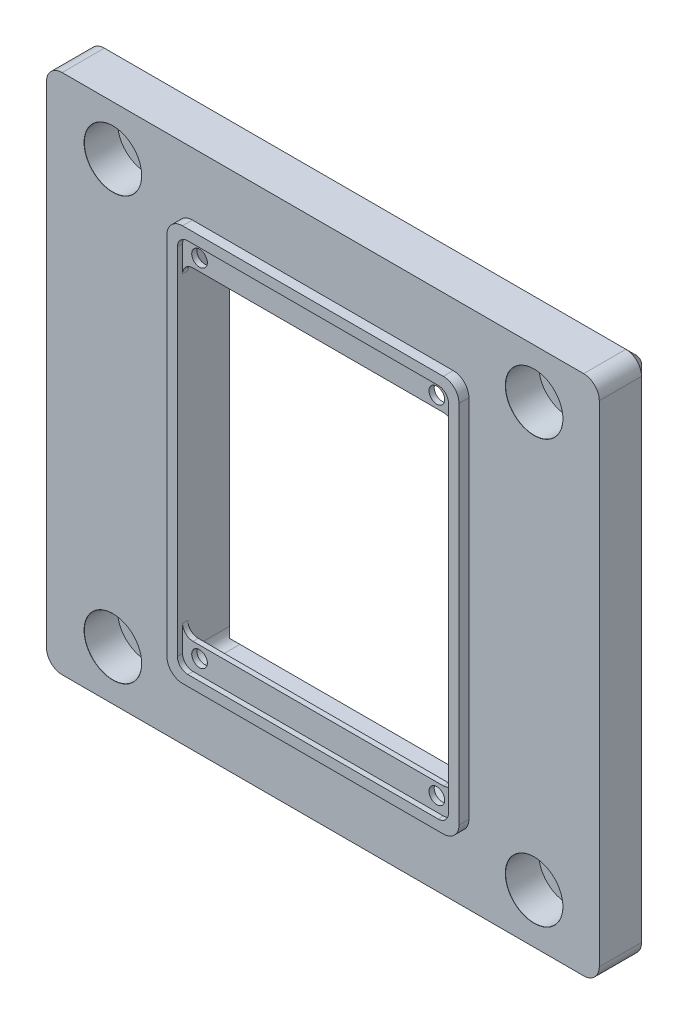
SolidWorks part; units mm, degrees
ref_plane "Front Plane" through (0, 0, 0) normal (1, 0, 0) x (0, 1, 0)
ref_plane "Top Plane" through (0, 0, 0) normal (0, 0, 1) x (0, 1, 0)
ref_plane "Right Plane" through (0, 0, 0) normal (0, 1, 0) x (-1, 0, 0)
sketch "Sketch1" plane through (0, 0, 0) normal (0, 0, 1) x (0, 1, 0)
  line L0 (33.4102, -36.8483) -> (45.4102, -61.8483)
  line L1 (-39.5237, 16.1988) -> (30.4763, 16.1988)
  line L2 (-39.5237, 16.1988) -> (-39.5237, -33.8012)
  line L3 (-39.5237, -33.8012) -> (30.4763, -33.8012)
  line L4 (30.4763, 16.1988) -> (30.4763, -33.8012)
  line L5 (-40.5898, 17.1517) -> (31.4102, 17.1517)
  line L6 (-40.5898, 17.1517) -> (-40.5898, -34.8483)
  line L7 (-40.5898, -34.8483) -> (31.4102, -34.8483)
  line L8 (31.4102, 17.1517) -> (31.4102, -34.8483)
  line L9 (-40.5898, 17.1517) -> (31.4102, -34.8483) construction
  line L10 (-40.5898, -34.8483) -> (31.4102, 17.1517) construction
  line L11 (-42.5898, -36.8483) -> (33.4102, -36.8483)
  line L12 (-42.5898, -36.8483) -> (-42.5898, 19.1517)
  line L13 (-42.5898, 19.1517) -> (33.4102, 19.1517)
  line L14 (33.4102, -36.8483) -> (33.4102, 19.1517)
  line L15 (-42.5898, -36.8483) -> (33.4102, 19.1517) construction
  line L16 (-42.5898, 19.1517) -> (33.4102, -36.8483) construction
  line L17 (-54.5898, 44.1517) -> (45.4102, 44.1517)
  line L18 (-54.5898, 44.1517) -> (-54.5898, -61.8483)
  line L19 (-54.5898, -61.8483) -> (45.4102, -61.8483)
  line L20 (45.4102, 44.1517) -> (45.4102, -61.8483)
  line L21 (-54.5898, 44.1517) -> (45.4102, -61.8483) construction
  line L22 (-54.5898, -61.8483) -> (45.4102, 44.1517) construction
  line L23 (45.4102, 44.1517) -> (33.4102, 19.1517)
  line L24 (39.4102, 31.6517) -> (39.4102, -49.3483)
  line L25 (39.4102, -49.3483) -> (39.4102, -61.8483)
  point P4 (-4.5898, -8.8483)
  point P9 (-4.5898, -8.8483)
  point P14 (-4.5898, -8.8483)
  dimension "D1" = 70
  dimension "D2" = 50
  dimension "D3" = 52
  dimension "D4" = 72
  dimension "D5" = 56
  dimension "D6" = 76
  dimension "D7" = 12.5
  dimension "D8" = 100
extrude "Boss-Extrude3" add sketch "Sketch1" along normal blind 10 and the other way blind 0.1 contours L20 L17 L18 L19 L14 L11 L12 L13 | L23 L24 L0 L20 | L24 L23 L14 L0 | L0 L25 L19 region at (8.8483, 36.5926, 0) region at (43.7289, 35.0964, 0) region at (8.8483, 42.5439, 0) region at (57.6817, 41.4102, 0)
sketch "Sketch5" plane through (0, 0, 10) normal (0, 0, 1) x (1, 0, 0)
  line L0 (49.3483, 39.4102) -> (49.3483, 35.9102)
  line L2 (-19.1517, -4.5898) -> (36.8483, -4.5898)
  line L3 (-19.1517, -42.5898) -> (-19.1517, 33.4102) construction
  line L4 (36.8483, -42.5898) -> (36.8483, 33.4102) construction
  point P1 (49.3483, 35.9102)
  point P6 (-31.4169, 35.9102)
  point P17 (-31.4169, -45.0898)
  point P18 (49.3483, -45.0898)
  dimension "D1" = 3.5
hole_wizard "CBORE for M6 Hex Socket Head Cap Screw2" positions "Sketch5" profile "Sketch6" counterbore size "M6" standard "ISO" end condition through all
sketch "Sketch6" plane through (49.3483, -45.0898, 10) normal (1, 0, 0) x (0, -1, 0)
  line L0 (0, 0) -> (0, 10.1)
  line L1 (0, 10.1) -> (3.3, 10.1)
  line L3 (3.3, 10.1) -> (3.3, 6.4)
  line L4 (5.5, 6.4) -> (3.3, 6.4)
  line L5 (5.5, 6.4) -> (5.5, 0.025)
  line L6 (5.5, 0.025) -> (5.525, 0)
  line L7 (5.525, 0) -> (0, 0)
  line L8 (-5.5, 0.025) -> (-5.525, 0) construction
  line L11 (0, -6.35) -> (0, 107.95) construction
  dimension "Thru Hole Dia." = 6.6
  dimension "Thru Hole Depth" = 10.1
  dimension "C'Bore Dia." = 11
  dimension "C'Bore Depth" = 6.4
  dimension "Near C'Sink Dia." = 11.05
  dimension "Near C'Sink Angle" = 90
sketch "Sketch7" plane through (0, 0, -0.1) normal (0, 0, -1) x (1, 0, 0)
  line L1 (-19.1517, 42.5898) -> (36.8483, 42.5898)
  line L2 (-19.1517, 42.5898) -> (-19.1517, -33.4102)
  line L3 (-19.1517, -33.4102) -> (36.8483, -33.4102)
  line L4 (36.8483, 42.5898) -> (36.8483, -33.4102)
extrude "Boss-Extrude4" add sketch "Sketch7" against normal blind 12
sketch "Sketch8" plane through (0, 0, 11.9) normal (0, 0, 1) x (1, 0, 0)
  line L1 (-17.1517, 31.4102) -> (34.8483, 31.4102)
  line L2 (-17.1517, 31.4102) -> (-17.1517, -40.5898)
  line L3 (-17.1517, -40.5898) -> (34.8483, -40.5898)
  line L4 (34.8483, 31.4102) -> (34.8483, -40.5898)
extrude "Boss-Extrude5" add sketch "Sketch8" against normal blind 1
sketch "Sketch9" plane through (0, 0, 11.9) normal (0, 0, 1) x (1, 0, 0)
  line L1 (-17.1517, 31.4102) -> (34.8483, 31.4102)
  line L2 (-17.1517, 31.4102) -> (-17.1517, -40.5898)
  line L3 (-17.1517, -40.5898) -> (34.8483, -40.5898)
  line L4 (34.8483, 31.4102) -> (34.8483, -40.5898)
extrude "Cut-Extrude1" cut sketch "Sketch9" against normal blind 1
sketch "Sketch10" plane through (0, 0, 10.9) normal (0, 0, 1) x (1, 0, 0)
  line L0 (34.8483, -40.5898) -> (34.8483, 31.4102) construction
  line L1 (-17.1517, 31.4102) -> (34.8483, 31.4102)
  line L2 (-17.1517, 31.4102) -> (-17.1517, 26.4148)
  line L3 (-17.1517, 26.4148) -> (34.8483, 26.4148)
  line L4 (34.8483, 31.4102) -> (34.8483, 26.4148)
  line L5 (-17.1517, -40.5898) -> (-17.1517, 31.4102) construction
  line L6 (34.8483, -40.5898) -> (-17.1517, -40.5898)
  line L7 (34.8483, -40.5898) -> (34.8483, -35.5907)
  line L8 (34.8483, -35.5907) -> (-17.1517, -35.5907)
  line L9 (-17.1517, -40.5898) -> (-17.1517, -35.5907)
  line L11 (-17.1517, 26.4148) -> (34.8483, 26.4148)
  line L12 (-17.1517, 26.4148) -> (-17.1517, -35.5907)
  line L13 (-17.1517, -35.5907) -> (34.8483, -35.5907)
  line L14 (34.8483, 26.4148) -> (34.8483, -35.5907)
  line M1 (-17.1517, 31.4102) -> (-17.1517, -40.5898)
  line M3 (34.8483, -40.5898) -> (34.8483, 31.4102)
extrude "Cut-Extrude2" cut sketch "Sketch10" against normal blind 11 contours L8 L3 M3 M1 region at (8.8483, -4.5879, 10.9)
sketch "Sketch11" plane through (0, 0, -0.1) normal (0, 0, -1) x (1, 0, 0)
  line L1 (-17.1517, 40.5898) -> (34.8483, 40.5898)
  line L2 (-17.1517, 40.5898) -> (-17.1517, 35.5907)
  line L3 (-17.1517, 35.5907) -> (34.8483, 35.5907)
  line L4 (34.8483, 40.5898) -> (34.8483, 35.5907)
  line L5 (-17.1517, -26.4148) -> (34.8483, -26.4148)
  line L6 (-17.1517, -26.4148) -> (-17.1517, -31.4102)
  line L7 (-17.1517, -31.4102) -> (34.8483, -31.4102)
  line L8 (34.8483, -26.4148) -> (34.8483, -31.4102)
extrude "Cut-Extrude3" cut sketch "Sketch11" against normal blind 10 contours L2 L1 L4 L3 | L6 L5 L8 L7
sketch "Sketch12" plane through (0, 0, 10.9) normal (0, 0, 1) x (1, 0, 0)
  line L0 (34.8483, -40.5898) -> (-17.1517, 31.4102) construction
  line L1 (-13.9017, 28.6602) -> (31.5983, 28.6602)
  line L2 (-13.9017, 28.6602) -> (-13.9017, -37.8398)
  line L3 (-13.9017, -37.8398) -> (31.5983, -37.8398)
  line L4 (31.5983, 28.6602) -> (31.5983, -37.8398)
  line L5 (-13.9017, 28.6602) -> (31.5983, -37.8398) construction
  line L6 (-13.9017, -37.8398) -> (31.5983, 28.6602) construction
  line L7 (-13.9017, -4.5898) -> (31.5983, -4.5898)
  line L8 (8.8483, 28.6602) -> (8.8483, -37.8398)
  circle A0 centre (-13.9017, -37.8398) radius 1.5
  circle A1 centre (31.5983, -37.8398) radius 1.5
  circle A2 centre (-13.9017, 28.6602) radius 1.5
  circle A3 centre (31.5983, 28.6602) radius 1.5
  point P0 (8.8483, -4.5898)
  dimension "D3" = 3
  dimension "D4" = 3
  dimension "D5" = 3
  dimension "D6" = 3
  dimension "D1" = 45.5
  dimension "D2" = 66.5
extrude "Cut-Extrude4" cut sketch "Sketch12" against normal blind 2 contours A2
extrude "Cut-Extrude5" cut sketch "Sketch12<3>" against normal blind 2 contours A3
sketch "Sketch12<3>" plane through (0, 0, 10.9) normal (0, 0, 1) x (1, 0, 0) same geometry as "Sketch12"
sketch "Sketch14" plane through (0, 0, 10.9) normal (0, 0, 1) x (1, 0, 0)
  circle A0 centre (-13.9017, -37.8398) radius 1.5
extrude "Cut-Extrude6" cut sketch "Sketch14" against normal blind 2
sketch "Sketch15" plane through (0, 0, 10.9) normal (0, 0, 1) x (1, 0, 0)
  circle A0 centre (31.5983, -37.8398) radius 1.5
extrude "Cut-Extrude7" cut sketch "Sketch15" against normal blind 2
fillet "Fillet2" radius 3 8 edges at (-44.1517, 45.4102, 4.95) (-19.1517, 33.4102, 10.95) (36.8483, 33.4102, 10.95) (61.8483, 45.4102, 4.95) (36.8483, -42.5898, 10.95) (61.8483, -54.5898, 4.95) (-44.1517, -54.5898, 4.95) (-19.1517, -42.5898, 10.95)
chamfer "Chamfer1" distance 2 angle 45 16 edges at (8.8483, 31.4102, -0.1) (34.8483, -4.5898, -0.1) (8.8483, -40.5898, -0.1) (-17.1517, -4.5898, -0.1) (52.6483, 35.9102, -0.1) (-28.1169, 35.9102, -0.1) (-28.1169, -45.0898, -0.1) (52.6483, -45.0898, -0.1) (-43.273, -53.7112, -0.1) (8.8483, -54.5898, -0.1) (60.9696, -53.7112, -0.1) (61.8483, -4.5898, -0.1) (60.9696, 44.5315, -0.1) (8.8483, 45.4102, -0.1) (-43.273, 44.5315, -0.1) (-44.1517, -4.5898, -0.1)
fillet "Fillet3" radius 2 1 edges at (34.8483, -35.5907, 10.4)
fillet "Fillet4" radius 2 11 edges at (-17.1517, 26.4148, 10.4) (-17.1517, 31.4102, 5.9) (-17.1517, 31.4102, 11.4) (34.8483, 31.4102, 5.9) (34.8483, 26.4148, 10.4) (34.8483, 31.4102, 11.4) (-17.1517, -40.5898, 5.9) (-17.1517, -40.5898, 11.4) (-17.1517, -35.5907, 10.4) (34.8483, -40.5898, 5.9) (34.8483, -40.5898, 11.4)
